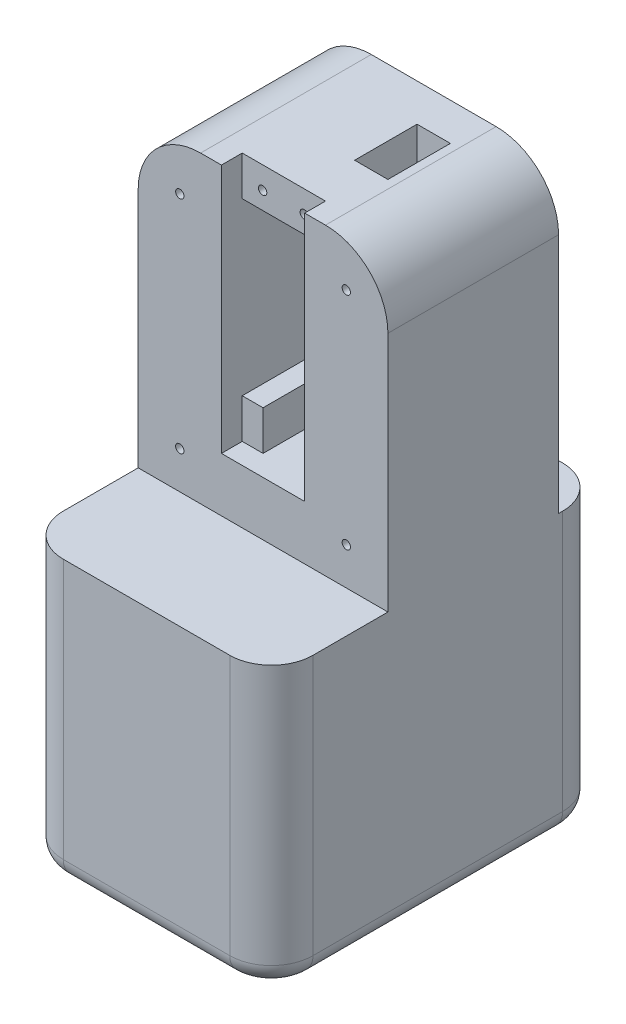
SolidWorks part; units mm, degrees
ref_plane "Front Plane" through (0, 0, 0) normal (0, 0, 1) x (1, 0, 0)
ref_plane "Top Plane" through (0, 0, 0) normal (0, 1, 0) x (1, 0, 0)
ref_plane "Right Plane" through (0, 0, 0) normal (1, 0, 0) x (0, 0, -1)
sketch "Sketch1" plane through (0, 0, 0) normal (0, 1, 0) x (1, 0, 0)
  circle A0 centre (0, 0) radius 25
extrude "Boss-Extrude1" add sketch "Sketch1" along normal blind 1
sketch "Sketch2" plane through (0, 1, 0) normal (0, 1, 0) x (1, 0, 0)
  line L1 (30, 40) -> (-30, 40)
  line L2 (30, 40) -> (30, -40)
  line L3 (30, -40) -> (-30, -40)
  line L4 (-30, 40) -> (-30, -40)
  line L5 (30, 40) -> (-30, -40) construction
  line L6 (30, -40) -> (-30, 40) construction
  point P0 (0, 0)
extrude "Boss-Extrude2" add sketch "Sketch2" along normal blind 80.5
fillet "Fillet1" radius 10 4 edges at (-30, 41.25, 40) (-30, 41.25, -40) (30, 41.25, 40) (30, 41.25, -40)
sketch "Sketch3" plane through (0, 81.5, 0) normal (0, 1, 0) x (1, 0, 0)
  line L0 (-20, -40) -> (20, -40) construction
  line L1 (30, 29) -> (-30, 29)
  line L2 (30, 29) -> (30, -12)
  line L3 (30, -12) -> (-30, -12)
  line L4 (-30, 29) -> (-30, -12)
  line L5 (20, 40) -> (-20, 40) construction
  line L7 (30, -30) -> (30, 30) construction
  line L8 (-30, 30) -> (-30, -30) construction
  point P0 (0, 0)
  dimension "D1" = 28
  dimension "D2" = 11
extrude "Boss-Extrude3" add sketch "Sketch3" along normal blind 60
sketch "Sketch4" plane through (0, 0, 12) normal (0, 0, 1) x (1, 0, 0)
  line L0 (-30, 141.5) -> (30, 81.5) construction
  line L5 (-30, 81.5) -> (30, 141.5) construction
  line L7 (10, 132) -> (-10, 132)
  line L8 (10, 132) -> (10, 91)
  line L9 (10, 91) -> (-10, 91)
  line L10 (-10, 132) -> (-10, 91)
  line L11 (10, 132) -> (-10, 91) construction
  line L12 (10, 91) -> (-10, 132) construction
  point P4 (0, 111.5)
extrude "Cut-Extrude1" cut sketch "Sketch4" against normal blind 32
sketch "Sketch5" plane through (0, 0, 12) normal (0, 0, 1) x (1, 0, 0)
  line L0 (-20, 81.5) -> (20, 81.5) construction
  line L1 (-10, 91) -> (10, 91)
  line L2 (-10, 91) -> (-10, 81.5)
  line L3 (-10, 81.5) -> (10, 81.5)
  line L4 (10, 91) -> (10, 81.5)
  line L5 (-30, 141.5) -> (30, 141.5) construction
  line L6 (-10, 132) -> (10, 132)
  line L7 (-10, 132) -> (-10, 141.5)
  line L8 (-10, 141.5) -> (10, 141.5)
  line L9 (10, 132) -> (10, 141.5)
extrude "Cut-Extrude2" cut sketch "Sketch5" against normal blind 5
sketch "Sketch6" plane through (0, 0, 12) normal (0, 0, 1) x (1, 0, 0)
  line L1 (10, 132) -> (-10, 132) construction
  point P0 (-0.1, 101)
  dimension "D1" = 31
ref_axis "Axis1" through (-0.1, 101, 12) along (0, 0, -1)
sketch "Sketch7" plane through (0, 0, -29) normal (0, 0, -1) x (-1, 0, 0)
  circle A0 centre (0.1, 101) radius 15
extrude "Cut-Extrude3" cut sketch "Sketch7" against normal blind 8 contours A0
sketch "Sketch8" plane through (0, 0, 12) normal (0, 0, 1) x (1, 0, 0)
  circle A0 centre (-0.1, 101) radius 21
extrude "Cut-Extrude4" cut sketch "Sketch8" along normal up to next
fillet "Fillet2" radius 15 2 edges at (-30, 141.5, -8.5) (30, 141.5, -8.5)
sketch "Sketch9" plane through (0, 0, -29) normal (0, 0, -1) x (-1, 0, 0)
  line L1 (32.6, 133.5) -> (-32.4, 133.5)
  line L2 (32.6, 133.5) -> (32.6, 68.5)
  line L3 (32.6, 68.5) -> (-32.4, 68.5)
  line L4 (-32.4, 133.5) -> (-32.4, 68.5)
  line L5 (32.6, 133.5) -> (-32.4, 68.5) construction
  line L6 (32.6, 68.5) -> (-32.4, 133.5) construction
extrude "Cut-Extrude5" cut sketch "Sketch9" along normal up to next
sketch "Sketch10" plane through (0, 0, 12) normal (0, 0, 1) x (1, 0, 0)
  line L1 (32.4, 133.5) -> (-32.6, 133.5)
  line L2 (32.4, 133.5) -> (32.4, 68.5)
  line L3 (32.4, 68.5) -> (-32.6, 68.5)
  line L4 (-32.6, 133.5) -> (-32.6, 68.5)
  line L5 (32.4, 133.5) -> (-32.6, 68.5) construction
  line L6 (32.4, 68.5) -> (-32.6, 133.5) construction
extrude "Cut-Extrude6" cut sketch "Sketch10" along normal up to next
fillet "Fillet3" radius 5 8 edges at (0, 1, -40) (27.0711, 1, -37.0711) (30, 1, 0) (27.0711, 1, 37.0711) (-27.0711, 1, -37.0711) (-30, 1, 0) (-27.0711, 1, 37.0711) (0, 1, 40)
sketch "Sketch11" plane through (0, 0, 0) normal (0, -1, 0) x (1, 0, 0)
  line L5 (7.5, 7.5) -> (-7.5, 7.5)
  line L6 (7.5, 7.5) -> (7.5, -7.5)
  line L7 (7.5, -7.5) -> (-7.5, -7.5)
  line L8 (-7.5, 7.5) -> (-7.5, -7.5)
  line L9 (7.5, 7.5) -> (-7.5, -7.5) construction
  line L10 (7.5, -7.5) -> (-7.5, 7.5) construction
  point P0 (0, 0)
extrude "Cut-Extrude7" cut sketch "Sketch11" against normal blind 20
fillet "Fillet5" radius 2 4 edges at (7.5, 10, 7.5) (7.5, 10, -7.5) (-7.5, 10, -7.5) (-7.5, 10, 7.5)
sketch "Sketch12" plane through (0, 0, 7) normal (0, 0, 1) x (1, 0, 0)
  line L0 (0, 91) -> (0, 81.5) construction
  line L1 (10, 91) -> (-10, 91) construction
  line L2 (-10, 81.5) -> (10, 81.5) construction
  line L3 (-10, 81.5) -> (10, 81.5) construction
  line L4 (5, 91) -> (-5, 91)
  line L5 (5, 91) -> (5, 81.5)
  line L6 (5, 81.5) -> (-5, 81.5)
  line L7 (-5, 91) -> (-5, 81.5)
  line L8 (5, 91) -> (-5, 81.5) construction
  line L9 (5, 81.5) -> (-5, 91) construction
  point P6 (0, 86.25)
extrude "Cut-Extrude8" cut sketch "Sketch12" against normal up to vertex (27 mm away) up to point (-10, 91, -20)
sketch "Sketch13" plane through (10, 0, 0) normal (-1, 0, 0) x (0, 0, 1)
  line L0 (-20, 91) -> (-20, 132) construction
  line L2 (-20, 99.6232) -> (-20, 81.5) construction
  line L3 (-20, 81.5) -> (12, 81.5) construction
  line L6 (-20, 81.5) -> (-5, 81.5)
  line L7 (-20, 81.5) -> (-20, 144.3822)
  line L8 (-20, 144.3822) -> (-5, 144.3822)
  line L9 (-5, 81.5) -> (-5, 144.3822)
extrude "Cut-Extrude9" cut sketch "Sketch13" against normal blind 3 and the other way up to vertex (5 mm away) other way up to point (5, 81.5, -20)
sketch "Sketch14" plane through (0, 0, 7) normal (0, 0, 1) x (1, 0, 0)
  circle A0 centre (4.9, 136.1896) radius 1
  circle A1 centre (-5.1, 136.1896) radius 1
extrude "Cut-Extrude10" cut sketch "Sketch14" against normal blind 10
sketch "Sketch15" plane through (0, 0, 12) normal (0, 0, 1) x (1, 0, 0)
  circle A0 centre (20, 77.5) radius 1
  circle A1 centre (-20, 77.5) radius 1
  circle A2 centre (-20, 130.5) radius 1
  circle A3 centre (20, 130.5) radius 1
extrude "Cut-Extrude11" cut sketch "Sketch15" against normal blind 10
